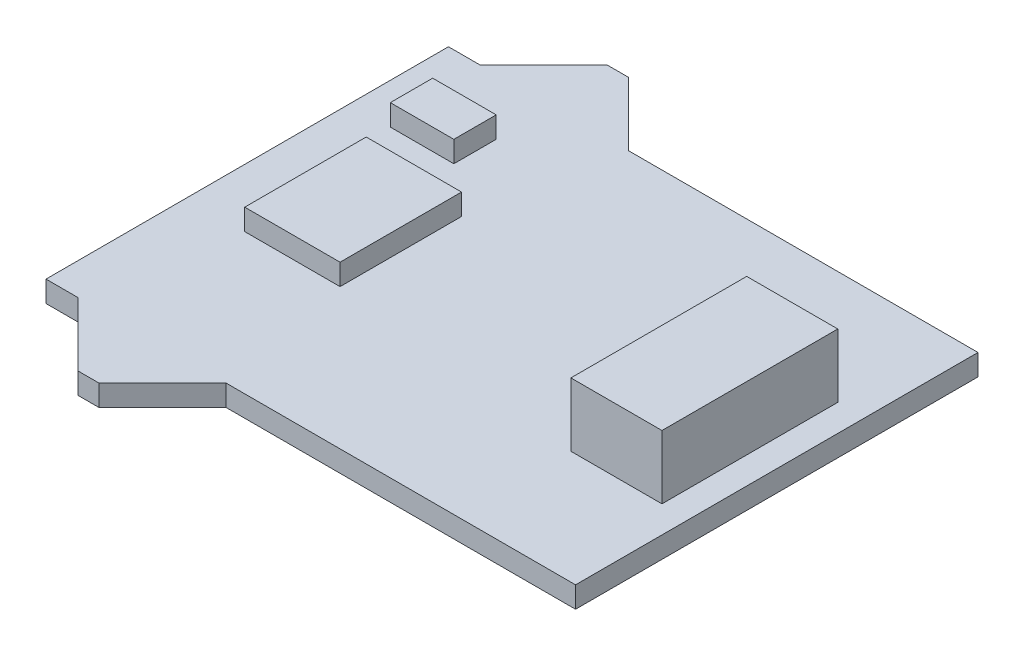
SolidWorks part; units mm, degrees
ref_plane "Front Plane" through (0, 0, 0) normal (0, 0, 1) x (1, 0, 0)
ref_plane "Top Plane" through (0, 0, 0) normal (0, 1, 0) x (1, 0, 0)
ref_plane "Right Plane" through (0, 0, 0) normal (1, 0, 0) x (0, 0, -1)
sketch "Sketch1" plane through (0, 0, 0) normal (0, 1, 0) x (1, 0, 0)
  line L0 (-3.5, 9.5) -> (-0.5, 12.5)
  line L1 (-5, -9.5) -> (5, -9.5) construction
  line L2 (-5, -9.5) -> (-5, 9.5) construction
  line L3 (-5, 9.5) -> (-3.5, 9.5)
  line L4 (5, -9.5) -> (5, 9.5) construction
  line L5 (-5, -9.5) -> (5, 9.5) construction
  line L6 (-5, 9.5) -> (5, -9.5) construction
  line L7 (-0.5, 12.5) -> (0.5, 12.5)
  line L8 (0.5, 12.5) -> (3.5, 9.5)
  line L9 (3.5, 9.5) -> (5, 9.5)
  line L10 (-5, 0) -> (5, 0) construction
  line L11 (3.5, -9.5) -> (5, -9.5)
  line L12 (5, 9.5) -> (20, 9.5)
  line L13 (5, 9.5) -> (5, -9.5) construction
  line L14 (5, -9.5) -> (20, -9.5)
  line L15 (20, 9.5) -> (20, -9.5)
  line L16 (0.5, -12.5) -> (3.5, -9.5)
  line L17 (-0.5, -12.5) -> (0.5, -12.5)
  line L18 (-5, -9.5) -> (-3.5, -9.5)
  line L19 (-3.5, -9.5) -> (-0.5, -12.5)
  line L20 (-5, 9.5) -> (-5, -9.5)
  point P0 (0, 0)
  point P8 (0, 12.5)
  dimension "D1" = 19
  dimension "D2" = 3
  dimension "D3" = 5
  dimension "D4" = 7
  dimension "D5" = 25
extrude "Boss-Extrude1" add sketch "Sketch1" against normal blind 1
sketch "Sketch2" plane through (0, 0, 0) normal (0, 1, 0) x (1, 0, 0)
  line L1 (-2.25, -2.8676) -> (2.25, -2.8676)
  line L2 (-2.25, -2.8676) -> (-2.25, 2.8676)
  line L3 (-2.25, 2.8676) -> (2.25, 2.8676)
  line L4 (2.25, -2.8676) -> (2.25, 2.8676)
  line L5 (-2.25, -2.8676) -> (2.25, 2.8676) construction
  line L6 (-2.25, 2.8676) -> (2.25, -2.8676) construction
  line L7 (-3.0875, 4.842) -> (-0.0875, 4.842)
  line L8 (-3.0875, 4.842) -> (-3.0875, 6.842)
  line L9 (-3.0875, 6.842) -> (-0.0875, 6.842)
  line L10 (-0.0875, 4.842) -> (-0.0875, 6.842)
  line L11 (-3.0875, 4.842) -> (-0.0875, 6.842) construction
  line L12 (-3.0875, 6.842) -> (-0.0875, 4.842) construction
  point P0 (0, 0)
  point P6 (-1.5875, 5.842)
  dimension "D1" = 5.7352
  dimension "D2" = 4.5
  dimension "D3" = 3
  dimension "D4" = 2
  dimension "D5" = 5.842
  dimension "D6" = 1.5875
extrude "Boss-Extrude2" add sketch "Sketch2" along normal blind 1
sketch "Sketch3" plane through (0, 0, 0) normal (0, 1, 0) x (1, 0, 0)
  line L5 (20, -9.5) -> (20, 9.5) construction
  line L6 (14.43, -4.15) -> (14.43, 4.15)
  line L8 (14.43, -4.15) -> (18.73, -4.15)
  line L9 (18.73, -4.15) -> (18.73, 4.15)
  line L10 (14.43, 4.15) -> (18.73, 4.15)
  point P8 (14.43, 0)
  dimension "D1" = 8.3
  dimension "D3" = 1.27
  dimension "D2" = 4.3
extrude "Boss-Extrude3" add sketch "Sketch3" along normal blind 3
sketch "Sketch4" plane through (0, 0, 0) normal (0, 1, 0) x (1, 0, 0)
  line L1 (17.8272, 3.99) -> (21.3134, 3.99)
  line L2 (17.8272, 3.99) -> (17.8272, -4.5386)
  line L3 (17.8272, -4.5386) -> (21.3134, -4.5386)
  line L4 (21.3134, 3.99) -> (21.3134, -4.5386)
extrude "Boss-Extrude4" [suppressed] add sketch "Sketch4" along normal blind 3
ref_axis "Axis1" through (0, -1.2, 0) along (0, 1, 0)
equation "\"width\"= 19mm"
equation "\"D1@Sketch1\"=\"width\""
equation "\"encoder_side_offse\"= 5mm"
equation "\"D3@Sketch1\"=\"encoder_side_offse\""
equation "\"nub_height\"= 3mm"
equation "\"D2@Sketch1\"=\"nub_height\""
equation "\"nub_width\"= 7mm"
equation "\"D4@Sketch1\"=\"nub_width\""
equation "\"pcb_length\"= 25mm"
equation "\"pcb_thickness\"= 1mm"
equation "\"D1@Boss-Extrude1\"=\"pcb_thickness\""
equation "\"encoder_width\"= 6mm"
equation "\"encoder_length\"= 4.5mm"
equation "\"D2@Sketch2\"=\"encoder_length\""
equation "\"plugin_side_offset\"= 1.5mm"
equation "\"connector_length\"= 4.3mm"
equation "\"D5@Sketch1\"=\"pcb_length\""
equation "\"connector_height\"= 3mm"
equation "\"connector_width\"= 8.3mm"
equation "\"D1@Sketch3\"=\"connector_width\""
equation "\"D1@Boss-Extrude3\"=\"connector_height\""
equation "\"D2@Sketch3\"=\"connector_length\""
